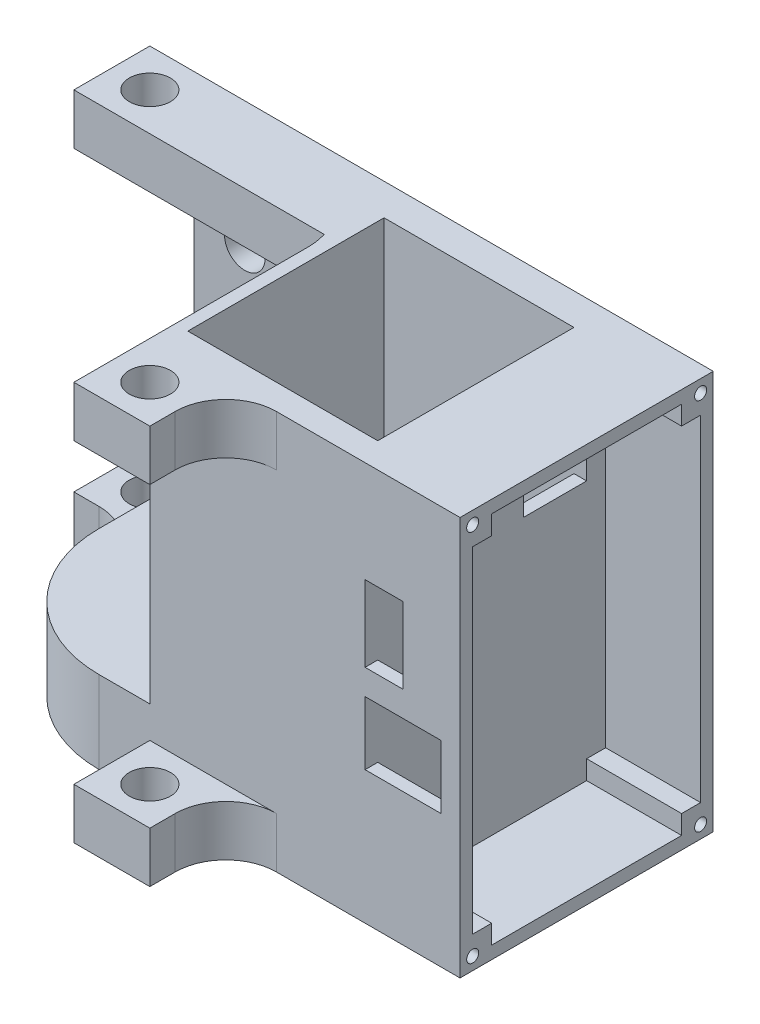
SolidWorks part; units mm, degrees
ref_plane "Front Plane" through (0, 0, 0) normal (0, 0, 1) x (1, 0, 0)
ref_plane "Top Plane" through (0, 0, 0) normal (0, 1, 0) x (1, 0, 0)
ref_plane "Right Plane" through (0, 0, 0) normal (1, 0, 0) x (0, 0, -1)
sketch "Sketch1" plane through (0, 0, 0) normal (0, 1, 0) x (1, 0, 0)
  line L0 (0, 0) -> (80, 0) construction
  line L1 (0, 20) -> (80, 20)
  line L2 (0, -20) -> (80, -20)
  line L3 (42, 20) -> (42, -20)
  line L4 (-20, 0) -> (0, 0)
  line L5 (-20, 0) -> (-20, 20)
  line L6 (-20, 20) -> (0, 20)
  line L7 (0, 0) -> (0, 20)
  circle A0 centre (0, 0) radius 7.11
  arc A1 (0, 20) -> (0, -20) centre (0, 0) ccw
  arc A2 (80, -20) -> (80, 20) centre (80, 0) ccw
  circle A4 centre (25, 0) radius 7.5
  point P3 (40, 0)
  dimension "D1" = 14.22
  dimension "D3" = 25
  dimension "D4" = 15
  dimension "D2" = 80
  dimension "D5" = 42
extrude "Boss-Extrude1" add sketch "Sketch1" along normal blind 5 contours A2 | A2 | A0 L0 A4 L3 L1 L7 | L0 A0 L4 A1 L2 L3 A4 | L7 A1 L4 A0 | A1 L6 L5 region at (21.5064, 0, -11.2354) region at (12.9405, 0, 10.6913) region at (-9.2797, 0, -9.2797) region at (-15.5326, 0, -15.5326)
sketch "Sketch2" plane through (0, 5, 0) normal (0, 1, 0) x (1, 0, 0)
  line L0 (-20, 20) -> (42, 20) construction
  line L1 (10, 20) -> (40, 20)
  line L2 (10, 20) -> (10, -20)
  line L3 (10, -20) -> (40, -20)
  line L4 (40, 20) -> (40, -20)
  line L5 (0, -20) -> (42, -20) construction
  circle A0 centre (25, 0) radius 12.5209
  dimension "D1" = 30
  dimension "D2" = 10
extrude "Boss-Extrude2" add sketch "Sketch2" along normal blind 8
sketch "Sketch3" plane through (0, 0, 0) normal (0, -1, 0) x (1, 0, 0)
  line L1 (13.5, -11.5) -> (36.5, -11.5) construction
  line L2 (13.5, -11.5) -> (13.5, 11.5) construction
  line L3 (13.5, 11.5) -> (36.5, 11.5) construction
  line L4 (36.5, -11.5) -> (36.5, 11.5) construction
  line L5 (13.5, -11.5) -> (36.5, 11.5) construction
  line L6 (13.5, 11.5) -> (36.5, -11.5) construction
  circle A0 centre (13.5, 11.5) radius 1.5
  circle A1 centre (36.5, 11.5) radius 1.5
  circle A2 centre (13.5, -11.5) radius 1.6909
  circle A3 centre (36.5, -11.5) radius 1.5
  point P0 (25, 0)
  dimension "D1" = 23
  dimension "D2" = 23
extrude "Cut-Extrude1" cut sketch "Sketch3" against normal through all
sketch "Sketch4" plane through (0, 0, 0) normal (0, -1, 0) x (1, 0, 0)
  circle A0 centre (13.5, 11.5) radius 3
  circle A1 centre (36.5, 11.5) radius 3
  circle A2 centre (36.5, -11.5) radius 3
  circle A3 centre (13.5, -11.5) radius 3
extrude "Cut-Extrude2" cut sketch "Sketch4" against normal blind 4
sketch "Sketch5" plane through (0, 0, 0) normal (0, 1, 0) x (1, 0, 0)
  line L1 (-20, 20) -> (42, 20)
  line L2 (-20, 20) -> (-20, 15)
  line L3 (-20, 15) -> (42, 15)
  line L4 (42, 20) -> (42, 15)
  line L5 (40, 20) -> (42, 20) construction
  line L6 (42, 20) -> (42, -20) construction
  line L7 (40, -20) -> (40, 20) construction
  line L8 (10, -20) -> (40, -20)
  line L9 (10, -20) -> (10, -16)
  line L10 (10, -16) -> (40, -16)
  line L11 (40, -20) -> (40, -16)
  dimension "D1" = 5
  dimension "D2" = 4
extrude "Boss-Extrude3" add sketch "Sketch5" along normal blind 55
sketch "Sketch6" plane through (0, 55, 0) normal (0, 1, 0) x (1, 0, 0)
  line L0 (10, 15) -> (10, -16) construction
  line L1 (-20, 20) -> (10, 20)
  line L2 (-20, 20) -> (-20, 0)
  line L3 (-20, 0) -> (10, 0)
  line L4 (10, 20) -> (10, 0)
  line L6 (10, 0) -> (0, 0)
  line L7 (10, 0) -> (10, -20)
  line L8 (10, -20) -> (0, -20)
  line L9 (0, 0) -> (0, -20)
  circle A0 centre (0, 0) radius 20
  point P12 (-20, 20)
  line M6 (-20, 20) -> (-20, 15)
  line M7 (-20, 15) -> (42, 15)
  line M9 (42, 20) -> (-20, 20)
extrude "Boss-Extrude4" add sketch "Sketch6" against normal blind 5 contours A0 L1 M6 M7 | A0 L2 M7 | L4 A0 M7 | A0 L4 M9 | A0 L3 L4 M7 | L9 A0 L7 L3 | A0 L8 L7 | L3 A0 L9 region at (-14.1001, 55, -17.8954) region at (7.5347, 55, -19.2063) region at (-0.5141, 55, -17.0796) region at (-18.0451, 55, -11.3888) region at (-4.0291, 55, -7.2106) region at (-8.4883, 55, 8.4883) region at (4.885, 55, 9.5824) region at (7.5347, 55, 19.2063)
sketch "Sketch7" plane through (0, 5, 0) normal (0, 1, 0) x (1, 0, 0)
  line L0 (40, -20) -> (0, -20) construction
  line L1 (10, 15) -> (8, 15)
  line L2 (10, 15) -> (10, -20)
  line L3 (10, -20) -> (8, -20)
  line L4 (8, 15) -> (8, -20)
  line L5 (40, -20) -> (40, 15) construction
  line L6 (40, 15) -> (42, 15)
  line L7 (40, 15) -> (40, -20)
  line L8 (40, -20) -> (42, -20)
  line L9 (42, 15) -> (42, -20)
  line L10 (10, 15) -> (42, 15) construction
  point P15 (42, -20)
  dimension "D1" = 2
  dimension "D2" = 2
extrude "Boss-Extrude5" add sketch "Sketch7" along normal blind 50
sketch "Sketch8" plane through (0, 0, -15) normal (0, 0, 1) x (1, 0, 0)
  line L0 (8, 5) -> (-20, 5) construction
  line L1 (-20, 50) -> (-20, 5) construction
  line L2 (-20, 50) -> (8, 50) construction
  circle A0 centre (-12, 15) radius 3.2
  circle A1 centre (-12, 40) radius 3.2
  point P4 (-10.8697, 18.8254)
  dimension "D1" = 10
  dimension "D2" = 10
  dimension "D3" = 8
extrude "Cut-Extrude3" cut sketch "Sketch8" against normal blind 50
sketch "Sketch9" plane through (0, 0, 0) normal (0, -1, 0) x (1, 0, 0)
  line L0 (0, 20) -> (42, 20) construction
  line L1 (25, 20) -> (42, 20)
  line L2 (25, 20) -> (25, -20)
  line L3 (25, -20) -> (42, -20)
  line L4 (42, 20) -> (42, -20)
  line L5 (25, 20) -> (0, 20)
  circle A0 centre (0, 0) radius 20
  circle A1 centre (25, 0) radius 12
  circle A2 centre (0, 0) radius 18
  circle A3 centre (25, 0) radius 10
  line M3 (-20, -20) -> (42, -20)
  line M6 (42, -20) -> (42, 20)
  line M7 (42, 20) -> (0, 20)
  arc M8 (0, 20) -> (-20, 0) centre (0, 0) ccw
  line M9 (-20, 0) -> (-20, -20)
  circle M12 centre (13.5, 11.5) radius 3
  circle M13 centre (36.5, 11.5) radius 3
  circle M14 centre (36.5, -11.5) radius 3
  circle M15 centre (13.5, -11.5) radius 3
extrude "Boss-Extrude6" add sketch "Sketch9" along normal blind 8 contours A2 A0 M12 M8 M15 | A2 A1 A0 M12 | A3 L2 A1 A0 | A3 A0 A1 A2 | A3 A2 A1 A0 | A2 A0 A1 M15 | A3 A0 A1 L2 | A3 L2 A1 | A1 L2 M3 M6 M7 M13 M14 | L4 L1 M6 | A0 M9 M3 | A1 L2 A0 M7 M12 region at (33.5, 0, 19.5654) region at (17.7227, 0, 16.2961) region at (33.2955, 0, 8.2955) region at (21.3918, 0, 10.1874) region at (7.2312, 0, 18.0842) region at (16.525, 0, 9.532) region at (17.2938, 0, 7.8055) region at (-15.5326, 0, -15.5326) region at (21.3918, 0, -10.1874) region at (17.2938, 0, -7.8055) region at (16.525, 0, -9.532)
sketch "Sketch10" plane through (42, 0, 0) normal (1, 0, 0) x (0, 0, -1)
  line L1 (-20, 55) -> (20, 55)
  line L2 (-20, 55) -> (-20, -8)
  line L3 (-20, -8) -> (20, -8)
  line L4 (20, 55) -> (20, -8)
  line L5 (-18, 53) -> (18, 53)
  line L6 (-18, 53) -> (-18, -6)
  line L7 (-18, -6) -> (18, -6)
  line L8 (18, 53) -> (18, -6)
  line L9 (-18, 53) -> (-15, 53)
  line L10 (-18, 53) -> (-18, 50)
  line L11 (-18, 50) -> (-15, 50)
  line L12 (-15, 53) -> (-15, 50)
  line L13 (18, 53) -> (15, 53)
  line L14 (18, 53) -> (18, 50)
  line L15 (18, 50) -> (15, 50)
  line L16 (15, 53) -> (15, 50)
  line L17 (-18, -6) -> (-15, -6)
  line L18 (-18, -6) -> (-18, -3)
  line L19 (-18, -3) -> (-15, -3)
  line L20 (-15, -6) -> (-15, -3)
  line L21 (18, -6) -> (15, -6)
  line L22 (18, -6) -> (18, -3)
  line L23 (18, -3) -> (15, -3)
  line L24 (15, -6) -> (15, -3)
  line M9 (20, 55) -> (-20, 55)
  line M10 (-20, 55) -> (-20, -8)
  line M11 (-20, -8) -> (20, -8)
  line M12 (20, -8) -> (20, 55)
  dimension "D1" = 2
  dimension "D2" = 2
  dimension "D3" = 2
  dimension "D4" = 2
  dimension "D5" = 3
  dimension "D6" = 3
  dimension "D7" = 3
  dimension "D8" = 3
  dimension "D9" = 3
  dimension "D10" = 3
  dimension "D11" = 3
  dimension "D12" = 3
extrude "Boss-Extrude7" add sketch "Sketch10" along normal blind 15 contours L5 L8 L7 L6 M12 M9 M10 M11 | L12 L5 L6 L11 | L5 L16 L15 L8 | L24 L7 L8 L23 | L7 L20 L19 L6 region at (42, 54.2537, 0) region at (42, 51.5, 16.5) region at (42, 51.5, -16.5) region at (42, -4.5, 16.5) region at (42, -4.5, -16.5)
sketch "Sketch11" plane through (42, 0, 0) normal (1, 0, 0) x (0, 0, -1)
  line L0 (15, 53) -> (-15, 53) construction
  line L1 (15, 50) -> (5, 50)
  line L2 (15, 50) -> (15, 35)
  line L3 (15, 35) -> (5, 35)
  line L4 (5, 50) -> (5, 35)
  line L5 (18, -3) -> (18, 50) construction
  dimension "D1" = 3
  dimension "D2" = 3
  dimension "D3" = 10
  dimension "D4" = 15
extrude "Cut-Extrude4" cut sketch "Sketch11" against normal blind 15
sketch "Sketch12" plane through (0, 0, 20) normal (0, 0, 1) x (1, 0, 0)
  line L1 (42, 39) -> (48, 39)
  line L2 (42, 39) -> (42, 27)
  line L3 (42, 27) -> (48, 27)
  line L4 (48, 39) -> (48, 27)
  line L5 (42, 23) -> (54, 23)
  line L6 (42, 23) -> (42, 13)
  line L7 (42, 13) -> (54, 13)
  line L8 (54, 23) -> (54, 13)
  line L9 (0, 55) -> (57, 55) construction
  line L10 (57, 55) -> (57, -8) construction
  dimension "D1" = 15
  dimension "D2" = 15
  dimension "D3" = 12
  dimension "D4" = 6
  dimension "D5" = 16
  dimension "D6" = 12
  dimension "D7" = 32
  dimension "D8" = 10
extrude "Cut-Extrude5" cut sketch "Sketch12" against normal blind 15
sketch "Sketch13" plane through (57, 0, 0) normal (1, 0, 0) x (0, 0, -1)
  line L0 (20, 55) -> (-20, 55) construction
  line L1 (-20, 55) -> (-20, -8) construction
  line L2 (20, -8) -> (20, 55) construction
  line L3 (-20, -8) -> (20, -8) construction
  circle A0 centre (-18, 53) radius 0.95
  circle A1 centre (18, 53) radius 0.95
  circle A2 centre (-18, -6) radius 0.95
  circle A3 centre (18, -6) radius 0.95
  dimension "D1" = 2
  dimension "D3" = 2
  dimension "D5" = 2
  dimension "D2" = 2
  dimension "D4" = 2
extrude "Cut-Extrude6" cut sketch "Sketch13" against normal blind 15
sketch "Sketch14" plane through (0, 55, 0) normal (0, 1, 0) x (1, 0, 0)
  line L0 (10, 15) -> (10, -16) construction
  line L1 (8, 15) -> (-24.4755, 15)
  line L2 (8, 15) -> (8, -23.9264)
  line L3 (8, -23.9264) -> (-24.4755, -23.9264)
  line L4 (-24.4755, 15) -> (-24.4755, -23.9264)
  line L5 (57, 20) -> (-20, 20) construction
  dimension "D1" = 2
  dimension "D2" = 5
extrude "Cut-Extrude7" cut sketch "Sketch14" against normal blind 15
sketch "Sketch15" plane through (0, 0, 0) normal (0, 1, 0) x (1, 0, 0)
  line L1 (8, -20) -> (20, -20)
  line L2 (8, -20) -> (8, -32)
  line L3 (8, -32) -> (20, -32)
  line L4 (20, -20) -> (20, -32)
  line L5 (-20, 20) -> (-32, 20)
  line L6 (-20, 20) -> (-20, 8)
  line L7 (-20, 8) -> (-32, 8)
  line L8 (-32, 20) -> (-32, 8)
  circle A0 centre (14, -26) radius 3.25
  circle A1 centre (-26, 14) radius 3.25
  dimension "D3" = 6.5
  dimension "D8" = 6.5
  dimension "D1" = 12
  dimension "D2" = 12
  dimension "D4" = 6
  dimension "D5" = 6
  dimension "D6" = 12
  dimension "D7" = 12
  dimension "D9" = 6
  dimension "D10" = 6
extrude "Boss-Extrude8" add sketch "Sketch15" against normal blind 8
pattern_linear "LPattern1" count 2 spacing 55 along (0, 1, 0) of "Boss-Extrude8"
sketch "Sketch16" plane through (0, 0, -15) normal (0, 0, 1) x (1, 0, 0)
  line L1 (-20, 55) -> (8, 55)
  line L2 (-20, 55) -> (-20, 47)
  line L3 (-20, 47) -> (8, 47)
  line L4 (8, 55) -> (8, 47)
extrude "Boss-Extrude9" add sketch "Sketch16" along normal blind 7
fillet "Fillet4" radius 8 3 edges at (20, -4, 20) (20, 51, 20) (-20, -4, -8)
fillet "Fillet5" radius 10 1 edges at (8, 26, -15)
